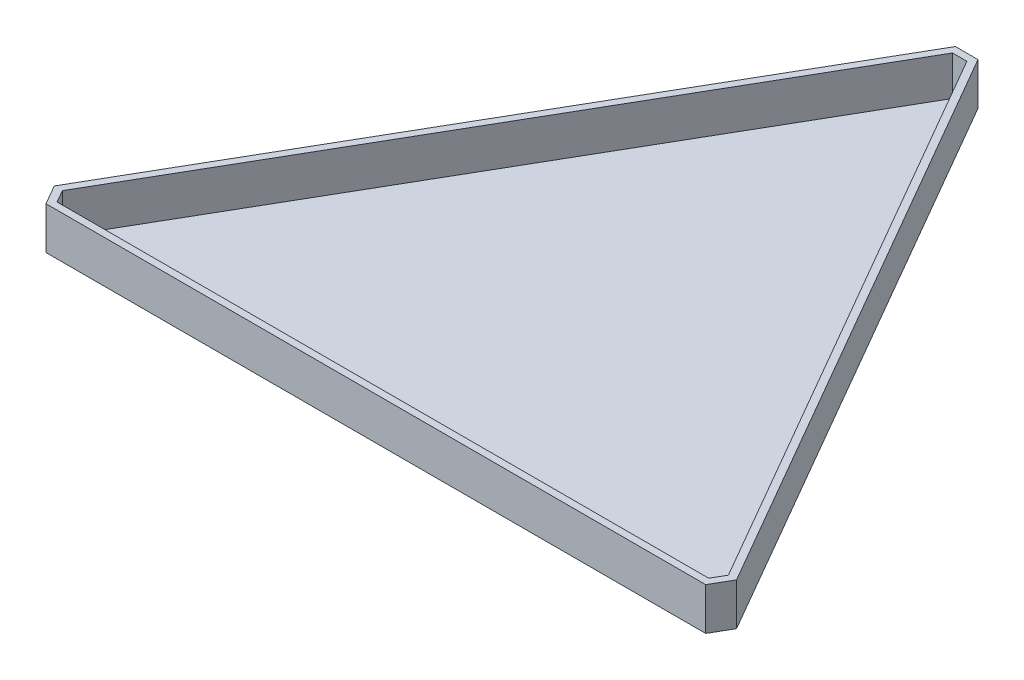
SolidWorks part; units mm, degrees
ref_plane "Front Plane" through (0, 0, 0) normal (0, 0, 1) x (1, 0, 0)
ref_plane "Top Plane" through (0, 0, 0) normal (0, 1, 0) x (1, 0, 0)
ref_plane "Right Plane" through (0, 0, 0) normal (1, 0, 0) x (0, 0, -1)
sketch "Sketch1" plane through (0, 0, 0) normal (0, 1, 0) x (1, 0, 0)
  line L0 (351.2729, 67.6655) -> (468.273, -134.9846)
  line L1 (347.2728, 67.6655) -> (347.2728, 65.1655) construction
  line L2 (409.773, -33.6595) -> (407.6079, -34.9095) construction
  line L3 (468.273, -134.9846) -> (464.2732, -141.9124)
  line L4 (230.2733, -141.9124) -> (464.2732, -141.9124)
  line L5 (230.2733, -141.9124) -> (226.2727, -134.9842)
  line L6 (226.2727, -134.9842) -> (343.2728, 67.6655)
  line L7 (353.4142, 63.9567) -> (351.2491, 62.7067) construction
  line L8 (347.2733, -141.9124) -> (347.2733, -139.4124) construction
  line L9 (231.7167, -139.4124) -> (462.8299, -139.4124)
  line L10 (284.7727, -33.6594) -> (286.9378, -34.9094) construction
  line L11 (344.7161, 65.1655) -> (349.8295, 65.1655)
  line L12 (465.3862, -134.9846) -> (349.8295, 65.1655)
  line L13 (466.2731, -138.4485) -> (464.1081, -137.1985) construction
  line L14 (462.8299, -139.4124) -> (465.3862, -134.9846)
  line L15 (229.1594, -134.9842) -> (344.7161, 65.1655)
  line L16 (229.1594, -134.9842) -> (231.7167, -139.4124)
  line L20 (343.2728, 67.6655) -> (351.2729, 67.6655)
  point P13 (407.6079, -34.9095)
  point P20 (464.1081, -137.1985)
  point P23 (347.2733, -139.4124)
  point P25 (347.2732, -141.9124)
  point P27 (347.2728, 65.1655)
  point P31 (286.9378, -34.9094)
  dimension "D1" = 2.5
  dimension "D2" = 2.5
  dimension "D3" = 2.5
  dimension "D4" = 2.5
  dimension "D5" = 2.5
  dimension "D6" = 2.5
extrude "Boss-Extrude6" add sketch "Sketch1" along normal blind 1 contours L16 L9 L14 L12 L11 L15
extrude "Boss-Extrude8" add sketch "Sketch1<7>" along normal blind 15
sketch "Sketch1<7>" plane through (0, 0, 0) normal (0, 1, 0) x (1, 0, 0) same geometry as "Sketch1"
